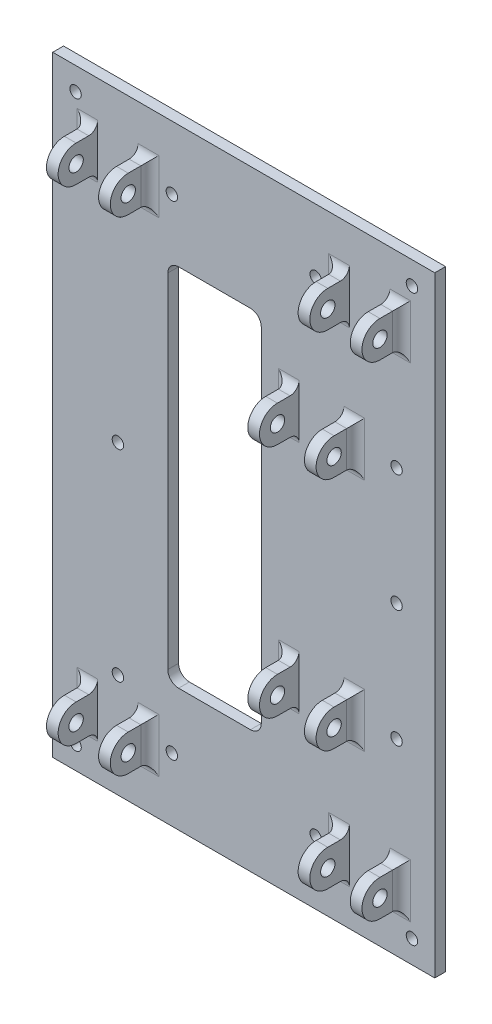
SolidWorks part; units mm, degrees
other "Markup3"
sketch "Sketch7" plane through (228.6, -342.9, 31.75) normal (0.076, -0.0024, 0.9971) x (0.9961, 0.0458, -0.0758)
other "Markup4"
sketch "Sketch8" plane through (228.6, -342.9, 31.75) normal (0.076, -0.0024, 0.9971) x (0.9961, 0.0458, -0.0758)
material "7075-T6 (SN)"
ref_plane "Front Plane" through (0, 0, 0) normal (0, 0, 1) x (1, 0, 0)
ref_plane "Top Plane" through (0, 0, 0) normal (0, 1, 0) x (1, 0, 0)
ref_plane "Right Plane" through (0, 0, 0) normal (1, 0, 0) x (0, 0, -1)
sketch "Sketch1" plane through (0, 0, 0) normal (0, 0, 1) x (1, 0, 0)
  line L1 (0, 0) -> (212.5, 0)
  line L2 (0, 0) -> (0, -339.725)
  line L3 (0, -339.725) -> (212.5, -339.725)
  line L4 (212.5, 0) -> (212.5, -339.725)
  dimension "D1" = 339.725
  dimension "D2" = 212.5
extrude "Boss-Extrude1" add sketch "Sketch1" along normal blind 6
sketch "Sketch2" plane through (0, 0, 6) normal (0, 0, 1) x (1, 0, 0)
  line L0 (0, 0) -> (0, -339.725) construction
  line L1 (25, -25.2425) -> (47.5, -25.2425) construction
  line L2 (25, -25.2425) -> (25, -45.2425)
  line L3 (25, -45.2425) -> (47.5, -45.2425) construction
  line L4 (47.5, -25.2425) -> (47.5, -45.2425)
  line L5 (165, -25.2425) -> (187.5, -25.2425) construction
  line L6 (165, -25.2425) -> (165, -45.2425)
  line L7 (165, -45.2425) -> (187.5, -45.2425) construction
  line L8 (187.5, -25.2425) -> (187.5, -45.2425)
  line L18 (137, -114.5325) -> (137, -225.1925) construction
  line L19 (0, -169.8625) -> (106.25, -169.8625) construction
  line L20 (54, -35.2425) -> (158.5, -35.2425) construction
  line L26 (165, -25.2425) -> (158.5, -25.2425)
  line L27 (165, -25.2425) -> (165, -45.2425)
  line L28 (165, -45.2425) -> (158.5, -45.2425)
  line L29 (158.5, -25.2425) -> (158.5, -45.2425)
  line L30 (187.5, -25.2425) -> (194, -25.2425)
  line L31 (187.5, -25.2425) -> (187.5, -45.2425)
  line L32 (187.5, -45.2425) -> (194, -45.2425)
  line L33 (194, -25.2425) -> (194, -45.2425)
  line L34 (47.5, -25.2425) -> (54, -25.2425)
  line L35 (47.5, -25.2425) -> (47.5, -45.2425)
  line L36 (47.5, -45.2425) -> (54, -45.2425)
  line L37 (54, -25.2425) -> (54, -45.2425)
  line L38 (25, -25.2425) -> (18.5, -25.2425)
  line L39 (25, -25.2425) -> (25, -45.2425)
  line L40 (25, -45.2425) -> (18.5, -45.2425)
  line L41 (18.5, -25.2425) -> (18.5, -45.2425)
  line L65 (212.5, -339.725) -> (212.5, 0) construction
  line L66 (137, -225.1925) -> (162, -225.1925) construction
  line L67 (158.5, -304.4825) -> (194, -304.4825) construction
  line L68 (149.5, -104.5325) -> (149.5, -235.1925) construction
  line L76 (18.5, -35.2425) -> (54, -35.2425) construction
  line L77 (18.5, -304.4825) -> (54, -304.4825) construction
  line L78 (36.25, -35.2425) -> (36.25, -304.4825) construction
  line L79 (137, -94.5325) -> (162, -94.5325) construction
  line L80 (54, -304.4825) -> (158.5, -304.4825) construction
  line L81 (106.25, -35.2425) -> (106.25, -304.4825) construction
  line L82 (106.25, -169.8625) -> (212.5, -169.8625) construction
  line L83 (130.5, -94.5325) -> (130.5, -114.5325)
  line L84 (137, -114.5325) -> (130.5, -114.5325)
  line L86 (137, -94.5325) -> (130.5, -94.5325)
  line L88 (137, -94.5325) -> (137, -114.5325)
  line L89 (162, -114.5325) -> (168.5, -114.5325)
  line L90 (162, -114.5325) -> (162, -94.5325)
  line L91 (168.5, -94.5325) -> (168.5, -114.5325)
  line L92 (162, -94.5325) -> (168.5, -94.5325)
  line L93 (130.5, -235.1925) -> (168.5, -235.1925) construction
  line L96 (137, -245.1925) -> (162, -245.1925) construction
  line L97 (162, -245.1925) -> (168.5, -245.1925)
  line L98 (168.5, -245.1925) -> (168.5, -225.1925)
  line L103 (130.5, -104.5325) -> (168.5, -104.5325) construction
  line L104 (137, -114.5325) -> (162, -114.5325) construction
  line L106 (158.5, -35.2425) -> (194, -35.2425) construction
  line L108 (176.25, -35.2425) -> (176.25, -304.4825) construction
  line L109 (165, -294.4825) -> (187.5, -294.4825) construction
  line L112 (165, -314.4825) -> (187.5, -314.4825) construction
  line L113 (25, -294.4825) -> (47.5, -294.4825) construction
  line L114 (25, -314.4825) -> (47.5, -314.4825) construction
  line L117 (162, -114.5325) -> (162, -225.1925) construction
  line L118 (18.5, -314.4825) -> (18.5, -294.4825)
  line L119 (25, -294.4825) -> (18.5, -294.4825)
  line L120 (25, -314.4825) -> (25, -294.4825)
  line L121 (25, -314.4825) -> (18.5, -314.4825)
  line L122 (54, -314.4825) -> (54, -294.4825)
  line L123 (47.5, -294.4825) -> (54, -294.4825)
  line L124 (47.5, -314.4825) -> (47.5, -294.4825)
  line L125 (47.5, -314.4825) -> (54, -314.4825)
  line L126 (194, -314.4825) -> (194, -294.4825)
  line L127 (187.5, -294.4825) -> (194, -294.4825)
  line L128 (187.5, -314.4825) -> (187.5, -294.4825)
  line L129 (187.5, -314.4825) -> (194, -314.4825)
  line L130 (158.5, -314.4825) -> (158.5, -294.4825)
  line L131 (165, -294.4825) -> (158.5, -294.4825)
  line L132 (165, -314.4825) -> (165, -294.4825)
  line L133 (165, -314.4825) -> (158.5, -314.4825)
  line L134 (187.5, -314.4825) -> (187.5, -294.4825)
  line L135 (165, -314.4825) -> (165, -294.4825)
  line L136 (47.5, -314.4825) -> (47.5, -294.4825)
  line L137 (25, -314.4825) -> (25, -294.4825)
  line L138 (162, -225.1925) -> (162, -245.1925)
  line L139 (162, -225.1925) -> (168.5, -225.1925)
  line L140 (137, -245.1925) -> (137, -225.1925)
  line L141 (137, -245.1925) -> (130.5, -245.1925)
  line L142 (137, -225.1925) -> (130.5, -225.1925)
  line L143 (130.5, -245.1925) -> (130.5, -225.1925)
  point P63 (194, -35.2425)
  point P101 (212.5, -169.8625)
  point P103 (158.5, -35.2425)
  dimension "D5" = 43.25
  dimension "D1" = 20
  dimension "D2" = 22.5
  dimension "D3" = 6.5
  dimension "D4" = 199.95
  dimension "D6" = 134.62
  dimension "D7" = 134.62
  dimension "D8" = 25
  dimension "D9" = 70
  dimension "D10" = 25
extrude "Boss-Extrude2" add sketch "Sketch2" along normal blind 24 contours L133 L132 L131 L130 | L128 L129 L126 L127 | L139 L138 L97 L98 | L143 L141 L140 L142 | L124 L125 L122 L123 | L121 L120 L119 L118 | L92 L90 L89 L91 | L88 L86 L83 L84 | L33 L30 L8 L32 | L37 L34 L4 L36 | L38 L41 L40 L2 | L26 L29 L28 L27 region at (21.75, -35.2425, 6) region at (50.75, -35.2425, 6) region at (190.75, -35.2425, 6) region at (133.75, -104.5325, 6) region at (165.25, -104.5325, 6) region at (165.25, -235.1925, 6) region at (21.75, -304.4825, 6) region at (50.75, -304.4825, 6) region at (190.75, -304.4825, 6) region at (161.75, -304.4825, 6) region at (133.75, -235.1925, 6)
sketch "Sketch3" plane through (18.5, 0, 0) normal (-1, 0, 0) x (0, 0, 1)
  line L0 (18, -104.5325) -> (6, -104.5325) construction
  line L1 (18, -304.4825) -> (6, -304.4825) construction
  line L2 (22, -235.1925) -> (37.7332, -235.1925) construction
  line L3 (22, -235.1925) -> (6, -235.1925) construction
  line L4 (18, -35.2425) -> (6, -35.2425) construction
  line L5 (6, -25.2425) -> (6, -45.2425) construction
  line L6 (6, -245.1925) -> (6, -225.1925) construction
  line L7 (6, 0) -> (6, -339.725) construction
  line L9 (18, -25.2425) -> (18, -12.9829)
  line L10 (18, -12.9829) -> (51.9495, -12.9829)
  line L11 (6, -245.1925) -> (6, -225.1925) construction
  line L12 (51.9495, -12.9829) -> (51.9495, -57.481)
  line L13 (51.9495, -57.481) -> (18, -57.481)
  line L14 (18, -57.481) -> (18, -45.2425)
  line L15 (52.4423, -132.3991) -> (18, -132.3991)
  line L16 (18, -94.5325) -> (18, -71.5915)
  line L17 (18, -71.5915) -> (52.4423, -71.5915)
  line L18 (18, -132.3991) -> (18, -114.5325)
  line L19 (52.4423, -71.5915) -> (52.4423, -132.3991)
  line L20 (52.5995, -270.3754) -> (18, -270.3754)
  line L21 (18, -225.1925) -> (18, -207.3064)
  line L22 (18, -207.3064) -> (52.5995, -207.3064)
  line L23 (18, -270.3754) -> (18, -245.1925)
  line L24 (52.5995, -207.3064) -> (52.5995, -270.3754)
  line L25 (52.621, -326.7211) -> (18, -326.7211)
  line L26 (18, -294.4825) -> (18, -282.2228)
  line L27 (18, -282.2228) -> (52.621, -282.2228)
  line L28 (18, -326.7211) -> (18, -314.4825)
  line L29 (52.621, -282.2228) -> (52.621, -326.7211)
  line L30 (6, -94.5325) -> (6, -114.5325) construction
  line L31 (30, -25.2425) -> (6, -25.2425) construction
  line L32 (30, -94.5325) -> (6, -94.5325) construction
  line L35 (6, -314.4825) -> (6, -294.4825) construction
  line L36 (6, -314.4825) -> (6, -294.4825) construction
  line L37 (18, -35.2425) -> (18, -104.5325) construction
  line L38 (18, -104.5325) -> (18, -235.1925) construction
  line L39 (18, -235.1925) -> (18, -304.4825) construction
  line L41 (30, -225.1925) -> (6, -225.1925) construction
  circle A0 centre (18, -35.2425) radius 4
  circle A1 centre (18, -235.1925) radius 4
  circle A2 centre (18, -35.2425) radius 5.5 construction
  circle A3 centre (18, -304.4825) radius 4
  circle A4 centre (18, -104.5325) radius 4
  arc A5 (18, -45.2425) -> (18, -25.2425) centre (18, -35.2425) ccw
  arc A6 (18, -114.5325) -> (18, -94.5325) centre (18, -104.5325) ccw
  arc A7 (18, -245.1925) -> (18, -225.1925) centre (18, -235.1925) ccw
  arc A8 (18, -314.4825) -> (18, -294.4825) centre (18, -304.4825) ccw
  point P62 (6, -304.4825)
  point P67 (6, -235.1925)
  dimension "D1" = 8
  dimension "D2" = 8
  dimension "D4" = 11
  dimension "D3" = 12
extrude "Cut-Extrude1" cut sketch "Sketch3" against normal through all both and the other way through all
fillet "Fillet2" radius 5 36 edges at (158.5, -304.4825, 6) (18.5, -304.4825, 6) (21.75, -45.2425, 6) (18.5, -35.2425, 6) (21.75, -25.2425, 6) (50.75, -25.2425, 6) (50.75, -45.2425, 6) (54, -35.2425, 6) (161.75, -25.2425, 6) (190.75, -25.2425, 6) (194, -35.2425, 6) (190.75, -45.2425, 6) (161.75, -45.2425, 6) (158.5, -35.2425, 6) (168.5, -104.5325, 6) (165.25, -114.5325, 6) (133.75, -114.5325, 6) (130.5, -104.5325, 6) (165.25, -94.5325, 6) (133.75, -94.5325, 6) (21.75, -294.4825, 6) (50.75, -294.4825, 6) (54, -304.4825, 6) (194, -304.4825, 6) (161.75, -294.4825, 6) (190.75, -294.4825, 6) (190.75, -314.4825, 6) (161.75, -314.4825, 6) (50.75, -314.4825, 6) (21.75, -314.4825, 6) (165.25, -225.1925, 6) (133.75, -225.1925, 6) (130.5, -235.1925, 6) (133.75, -245.1925, 6) (165.25, -245.1925, 6) (168.5, -235.1925, 6)
sketch "Sketch5" plane through (0, 0, 6) normal (0, 0, 1) x (1, 0, 0)
  line L0 (212.5, 0) -> (0, 0) construction
  line L1 (0, 0) -> (0, -339.725) construction
  line L2 (212.5, -339.725) -> (212.5, 0) construction
  line L5 (0, -169.8625) -> (212.5, -169.8625) construction
  line L6 (153.5, -35.2425) -> (59, -35.2425) construction
  line L7 (59, -20.2425) -> (59, -50.2425) construction
  line L8 (191.25, -104.5325) -> (191.25, -169.8625) construction
  line L9 (13.5, -50.2425) -> (59, -50.2425) construction
  line L10 (25, -50.2425) -> (13.5, -50.2425) construction
  line L11 (36.25, -50.2425) -> (36.25, -169.8625) construction
  line L12 (191.25, -169.8625) -> (191.25, -235.1925) construction
  line L15 (173.5, -89.5325) -> (173.5, -119.5325) construction
  line L16 (106.25, 0) -> (106.25, -339.725) construction
  line L17 (173.5, -104.5325) -> (191.25, -104.5325) construction
  line L26 (0, -339.725) -> (212.5, -339.725) construction
  circle A0 centre (12.7, -12.7) radius 3.175
  circle A1 centre (199.8, -12.7) radius 3.175
  circle A2 centre (66.25, -35.2425) radius 3.175
  circle A3 centre (146.25, -35.2425) radius 3.175
  circle A4 centre (176.25, -57.8625) radius 3.175
  circle A5 centre (36.25, -57.8625) radius 3.175
  circle A6 centre (191.25, -104.5325) radius 3.175
  circle A7 centre (36.25, -169.8625) radius 3.175
  circle A8 centre (191.25, -169.8625) radius 3.175
  circle A9 centre (36.25, -281.8625) radius 3.175
  circle A10 centre (66.25, -304.4825) radius 3.175
  circle A11 centre (12.7, -327.025) radius 3.175
  circle A12 centre (199.8, -327.025) radius 3.175
  circle A13 centre (146.25, -304.4825) radius 3.175
  circle A15 centre (191.25, -235.1925) radius 3.175
  dimension "D1" = 93.55
  dimension "D3" = 40
  dimension "D5" = 85
  dimension "D8" = 6.35
  dimension "D2" = 157.1625
  dimension "D4" = 112
extrude "Cut-Extrude2" cut sketch "Sketch5" against normal through all contours A0 | A5 | A3 | A1 | A4 | A6 | A7 | A8 | A12 | A13 | A10 | A9 | A11 | A15 | A2 region at (12.7, -12.7, 6) region at (199.8, -12.7, 6) region at (146.25, -35.2425, 6) region at (176.25, -57.8625, 6) region at (36.25, -57.8625, 6) region at (191.25, -104.5325, 6) region at (36.25, -169.8625, 6) region at (191.25, -169.8625, 6) region at (36.25, -281.8625, 6) region at (66.25, -304.4825, 6) region at (12.7, -327.025, 6) region at (199.8, -327.025, 6) region at (146.25, -304.4825, 6)
sketch "Sketch9" plane through (0, 0, 6) normal (0, 0, 1) x (1, 0, 0)
  line L0 (0, -169.8625) -> (212.5, -169.8625) construction
  line L11 (0, 0) -> (0, -339.725) construction
  line L12 (212.5, -339.725) -> (212.5, 0) construction
  line L14 (70, -271.3625) -> (110, -271.3625)
  line L15 (64, -265.3625) -> (64, -74.3625)
  line L16 (70, -68.3625) -> (110, -68.3625)
  line L17 (116, -265.3625) -> (116, -74.3625)
  line L18 (64, -271.3625) -> (116, -68.3625) construction
  line L19 (64, -68.3625) -> (116, -271.3625) construction
  arc A0 (110, -271.3625) -> (116, -265.3625) centre (110, -265.3625) ccw
  arc A1 (70, -271.3625) -> (64, -265.3625) centre (70, -265.3625) cw
  arc A2 (64, -74.3625) -> (70, -68.3625) centre (70, -74.3625) cw
  arc A5 (110, -68.3625) -> (116, -74.3625) centre (110, -74.3625) cw
  point P6 (90, -169.8625)
  point P22 (169.7848, -178.533)
  point P23 (214.9568, -251.8775)
  point P24 (158.9712, -185.193)
  point P25 (204.1432, -258.5375)
  dimension "D1" = 90
  dimension "D3" = 52
  dimension "D4" = 6
  dimension "D2" = 203
extrude "Cut-Extrude3" cut sketch "Sketch9" against normal through all contours L15 A2 L16 A5 L17 A0 L14 A1
sketch3d "3DSketch1"
  line L0 (18.5, -35.2425, 18) -> (194, -35.2425, 18) construction
  line L1 (25, -35.2425, 18) -> (18.5, -35.2425, 18) construction
  line L2 (194, -35.2425, 18) -> (187.5, -35.2425, 18) construction
  line L3 (194, -35.2425, 18) -> (187.5, -35.2425, 18) construction
  line L5 (194, -304.4825, 18) -> (187.5, -304.4825, 18) construction
  line L6 (194, -304.4825, 18) -> (18.5, -304.4825, 18) construction
  line L7 (25, -304.4825, 18) -> (18.5, -304.4825, 18) construction
  circle A0 centre (194, -35.2425, 18) radius 4 construction
  point P17 (198, -35.2425, 18)
  point P18 (194, -35.2425, 18)
